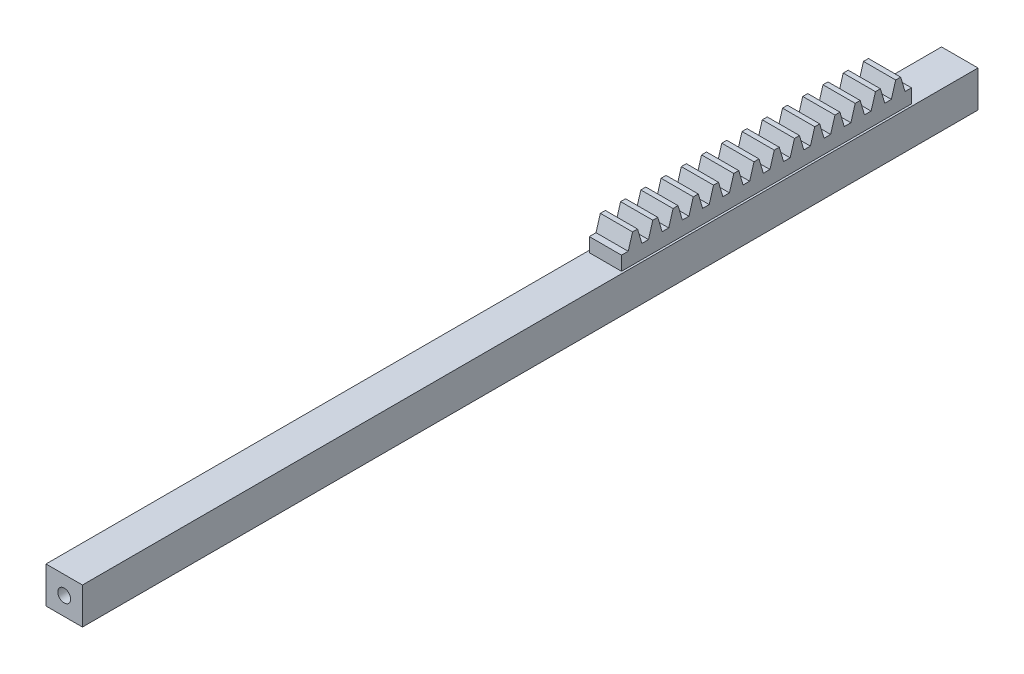
SolidWorks part; units mm, degrees
ref_plane "Plan de face" through (0, 0, 0) normal (0, 0, 1) x (1, 0, 0)
ref_plane "Plan de dessus" through (0, 0, 0) normal (0, 1, 0) x (1, 0, 0)
ref_plane "Plan de droite" through (0, 0, 0) normal (1, 0, 0) x (0, 0, -1)
sketch "Esquisse1" plane through (0, 0, 0) normal (0, 1, 0) x (1, 0, 0)
  line L1 (2.5, -22.5) -> (-2.5, -22.5)
  line L2 (2.5, -22.5) -> (2.5, 22.5)
  line L3 (2.5, 22.5) -> (-2.5, 22.5)
  line L4 (-2.5, -22.5) -> (-2.5, 22.5)
  line L5 (2.5, -22.5) -> (-2.5, 22.5) construction
  line L6 (2.5, 22.5) -> (-2.5, -22.5) construction
  point P0 (0, 0)
  dimension "D1" = 5
  dimension "D2" = 45
extrude "Boss.-Extru.1" add sketch "Esquisse1" along normal blind 5
sketch "Esquisse7" plane through (0, 0, -22.5) normal (0, 0, -1) x (-1, 0, 0)
  line L1 (2.8284, -2.8284) -> (-2.8284, -2.8284)
  line L2 (2.8284, -2.8284) -> (2.8284, 2.8284)
  line L3 (2.8284, 2.8284) -> (-2.8284, 2.8284)
  line L4 (-2.8284, -2.8284) -> (-2.8284, 2.8284)
  line L5 (2.8284, -2.8284) -> (-2.8284, 2.8284) construction
  line L6 (2.8284, 2.8284) -> (-2.8284, -2.8284) construction
  point P0 (0, 0)
  dimension "D1" = 8
extrude "Carré" add sketch "Esquisse7" against normal blind 129 and the other way blind 10 contours L2 L1 L4 L3
sketch "Esquisse2" plane through (0, 0, -22.5) normal (0, 0, -1) x (-1, 0, 0)
  circle A0 centre (0, 0) radius 4
  dimension "D1" = 8
extrude "Circulaire" [suppressed] add sketch "Esquisse2" against normal blind 129 and the other way blind 10 contours A0
sketch "Esquisse3" plane through (0, 0, 0) normal (1, 0, 0) x (0, 0, -1)
  line L0 (-22.5, 5) -> (22.5, 5) construction
  line L1 (20.4405, 7.2736) -> (20.4405, 5) construction
  line L2 (19.3811, 5) -> (21.5, 5)
  line L3 (22.5, 5) -> (22.5, 2.8284) construction
  line L4 (19.3811, 5) -> (20.0528, 7.2708)
  line L5 (20.8282, 7.2708) -> (21.5, 5)
  arc A6 (20.8282, 7.2708) -> (20.0528, 7.2708) centre (20.4405, -18.7264) ccw
  dimension "D1" = 26
  dimension "D2" = 2.2708
  dimension "D4" = 0.7754
  dimension "D6" = 1
  dimension "D3" = 0.6718
extrude "Boss.-Extru.3" add sketch "Esquisse3" along normal up to surface and the other way up to surface up to face at (2.5, 3.9142, 0) other way up to face at (-2.5, 3.9142, 0)
pattern_linear "Répétition linéaire1" count 14 spacing 3.1416 along (0, 0, 1) of "Boss.-Extru.3"
sketch "Esquisse5" [suppressed] plane through (0, 0, 106.5) normal (0, 0, 1) x (1, 0, 0)
  circle A0 centre (0, 0) radius 1
  dimension "D1" = 2
extrude "Enlèv. mat.-Extru.1" [suppressed] cut sketch "Esquisse5" against normal blind 10
sketch "Esquisse6" [suppressed] plane through (0, 0, -32.5) normal (0, 0, -1) x (-1, 0, 0)
  circle A0 centre (0, 0) radius 1
  circle A1 centre (0, 0) radius 1 construction
extrude "Enlèv. mat.-Extru.2" [suppressed] cut sketch "Esquisse6" against normal blind 10
sketch "Esquisse8" plane through (0, 0, -32.5) normal (0, 0, -1) x (-1, 0, 0)
  circle A0 centre (0, 0) radius 1
  dimension "D1" = 2
extrude "Enlèv. mat.-Extru.3" cut sketch "Esquisse8" against normal blind 10
sketch "Esquisse9" plane through (0, 0, 106.5) normal (0, 0, 1) x (1, 0, 0)
  circle A0 centre (0, 0) radius 1
  dimension "D1" = 2
extrude "Enlèv. mat.-Extru.4" cut sketch "Esquisse9" against normal blind 10
